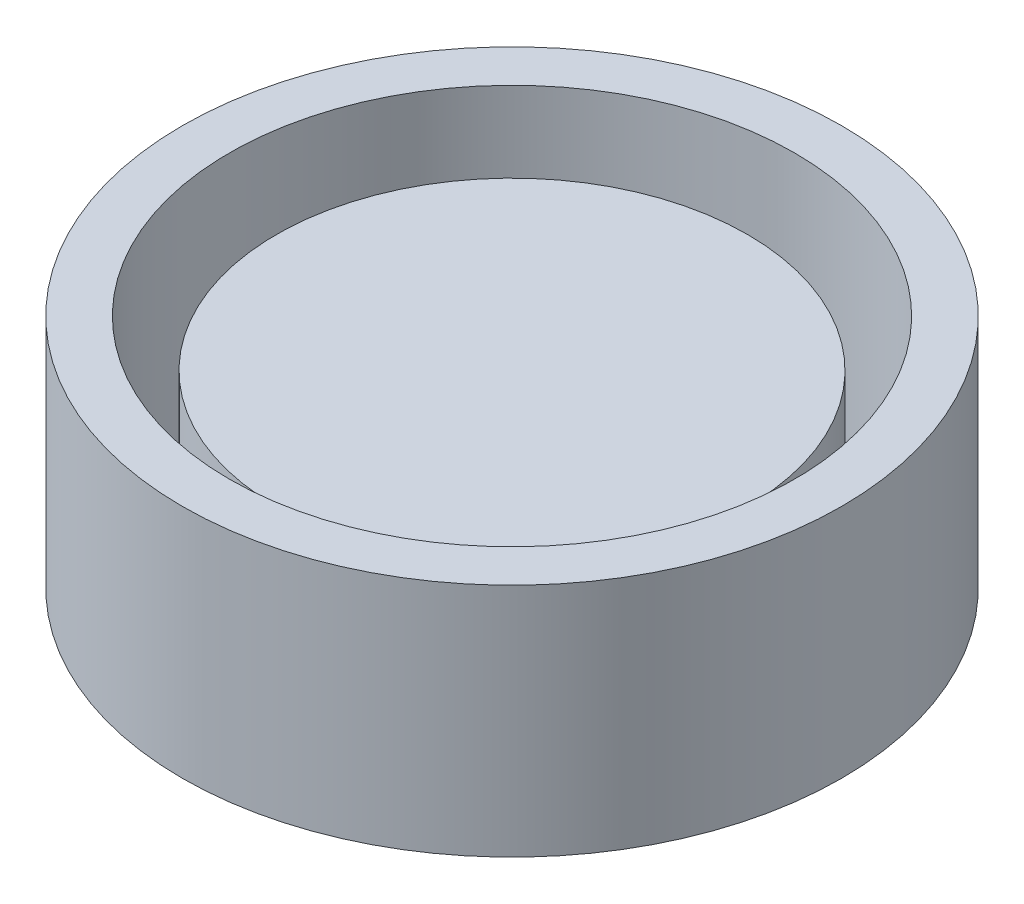
SolidWorks part; units mm, degrees
ref_plane "Front" through (0, 0, 0) normal (0, 0, 1) x (1, 0, 0)
ref_plane "Top" through (0, 0, 0) normal (0, 1, 0) x (1, 0, 0)
ref_plane "Right" through (0, 0, 0) normal (1, 0, 0) x (0, 0, -1)
sketch "Base" plane through (0, 0, 0) normal (0, 1, 0) x (1, 0, 0)
  circle A0 centre (0, 0) radius 5000
  circle A1 centre (0, 0) radius 6000
  circle A2 centre (0, 0) radius 7000
  dimension "D1" = 10000
  dimension "D2" = 12000
  dimension "D3" = 14000
extrude "Ground" add sketch "Base" along normal blind 4000 contours A0 region at (0, 0, 0)
extrude "Wall" add sketch "Sketch1<3>" along normal blind 5000 separate body contours A2 A1 region at (-6802.0101, 0, 0)
sketch "Sketch1<3>" plane through (0, 0, 0) normal (0, 1, 0) x (1, 0, 0) same geometry as "Base"
